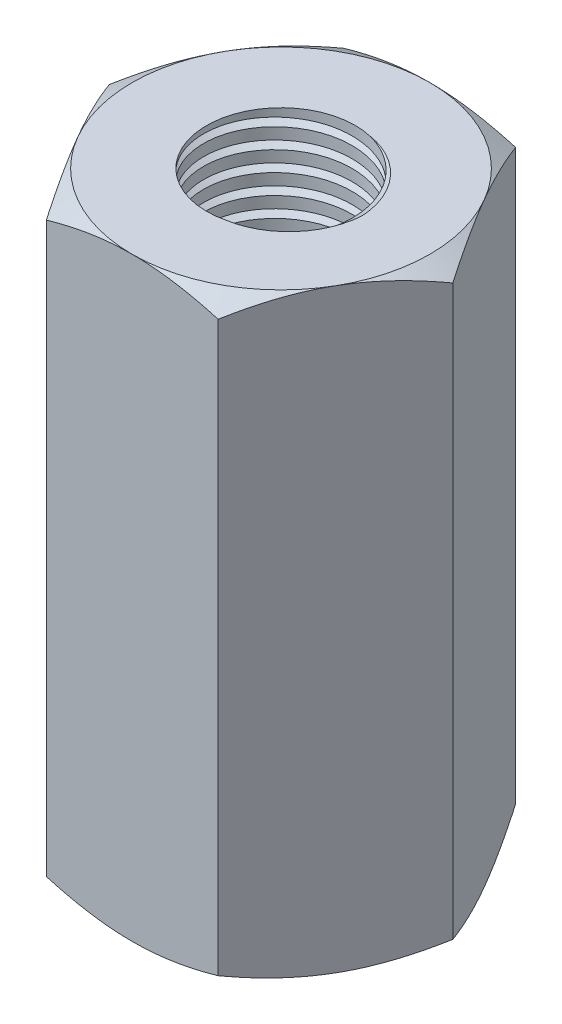
SolidWorks part; units mm, degrees
ref_plane "Front Plane" through (0, 0, 0) normal (0, 0, 1) x (1, 0, 0)
ref_plane "Top Plane" through (0, 0, 0) normal (0, 1, 0) x (1, 0, 0)
ref_plane "Right Plane" through (0, 0, 0) normal (1, 0, 0) x (0, 0, -1)
sketch "Sketch1" plane through (0, 0, 0) normal (0, 1, 0) x (1, 0, 0)
  line L1 (3.4641, 0) -> (1.7321, 3)
  line L2 (1.7321, 3) -> (-1.7321, 3)
  line L3 (-1.7321, 3) -> (-3.4641, 0)
  line L4 (-3.4641, 0) -> (-1.7321, -3)
  line L5 (-1.7321, -3) -> (1.7321, -3)
  line L6 (1.7321, -3) -> (3.4641, 0)
  circle A0 centre (0, 0) radius 3 construction
  circle A1 centre (0, 0) radius 1.5
extrude "Boss-Extrude1" add sketch "Sketch1" along normal blind 12
sketch "Sketch2" plane through (0, 12, 0) normal (0, 1, 0) x (1, 0, 0)
  circle A0 centre (0, 0) radius 3
extrude "Cut-Extrude2" cut sketch "Sketch2" against normal blind 1 draft 60 flip side to cut
sketch "Sketch4" plane through (0, 0, 0) normal (0, -1, 0) x (1, 0, 0)
  circle A0 centre (0, 0) radius 3
extrude "Cut-Extrude3" cut sketch "Sketch4" against normal blind 1 draft 60 flip side to cut
sketch "Sketch5" plane through (0, 0, 0) normal (0, -1, 0) x (-1, 0, 0)
  circle A0 centre (0, 0) radius 1.5
curve "Helix/Spiral1" pitch 0.4 height 13.5 turns 33.75
sketch3d "3DSketch2"
  line L7 (0, 13.3313, 1.3539) -> (0, 13.6687, 1.3539)
  line L8 (0, 13.5, 1.6461) -> (0, 13.3313, 1.3539)
  line L9 (0, 13.6687, 1.3539) -> (0, 13.5, 1.6461)
sweep "Cut-Sweep1" cut profiles "3DSketch2" path "Helix/Spiral1"
